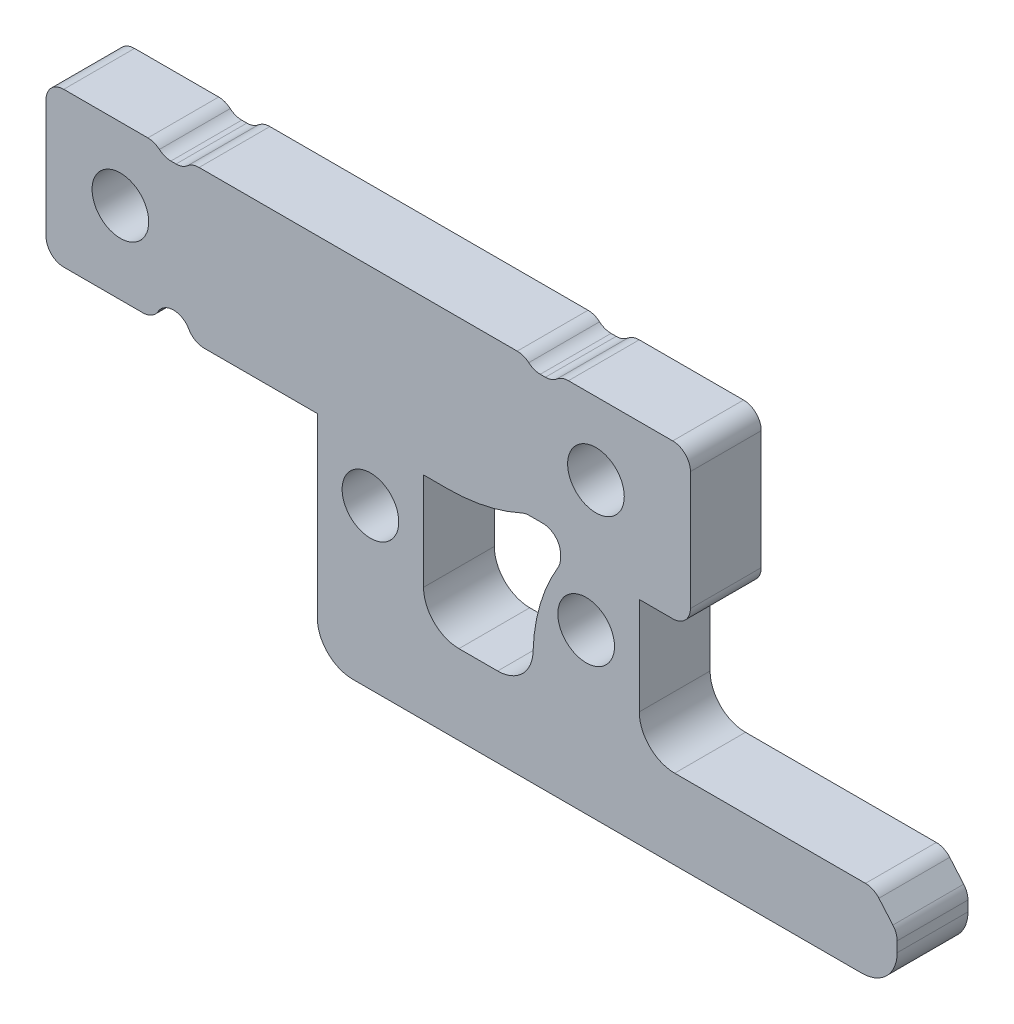
SolidWorks part; units mm, degrees
ref_plane "Plano frontal" through (0, 0, 0) normal (0, 0, 1) x (1, 0, 0)
ref_plane "Plano superior" through (0, 0, 0) normal (0, 1, 0) x (1, 0, 0)
ref_plane "Plano direito" through (0, 0, 0) normal (1, 0, 0) x (0, 0, -1)
sketch "Sketch1" plane through (0, 0, 0) normal (0, 0, 1) x (1, 0, 0)
  line L0 (4.8571, -7) -> (4.8571, 0.8881) construction
  line L2 (-4.2359, -11.5003) -> (-4.2359, 0.5)
  line L3 (1.7641, 0.5) -> (1.7641, -7)
  line L4 (-4.2359, -11.5) -> (-4.2359, -11.5003)
  line L5 (7.95, 0.5) -> (1.7641, 0.5)
  line L6 (16.8395, 9.2) -> (-19.5605, 9.2)
  line L7 (16.8395, 9.2) -> (16.8395, 0.5)
  line L8 (7.95, 0.5) -> (7.95, -7)
  line L9 (16.8395, 0.5) -> (13.95, 0.5)
  line L10 (13.95, -7) -> (13.95, 0.5)
  line L11 (-4.2359, 0.5) -> (-19.5605, 0.5)
  line L12 (-19.5605, 9.2) -> (-19.5605, 0.5)
  line L43 (28.5174, -11.5) -> (28.5174, -8.5479)
  line L44 (28.5174, -8.5479) -> (27.1867, -7)
  line L45 (27.1867, -7) -> (13.95, -7)
  line L49 (28.5174, -11.5) -> (-4.2359, -11.5)
  line L53 (7.95, -7) -> (1.7641, -7)
extrude "Boss-Extrude1" add sketch "Sketch1" along normal blind 4 contours L8 L53 L3 L2 L49 L43 L44 L45 L10 region at (-3.7124, -5.5, 0)
fillet "Fillet1" radius 2 5 edges at (28.5174, -11.5, 2) (13.95, -7, 2) (7.95, -7, 2) (-4.2359, -11.5, 2) (1.7641, -7, 2)
hole_wizard "M3 Clearance Hole1" positions "Sketch3" profile "Sketch2" hole size "M3" standard "ISO" end condition through all
sketch "Sketch3" plane through (0, 0, 4) normal (0, 0, 1) x (1, 0, 0)
  line L0 (4.8571, -7) -> (4.8571, -5.6319) construction
  line L1 (5.95, -7) -> (3.7641, -7) construction
  point P0 (10.95, -2.5)
  point P6 (-1.2359, -2.5)
  point P7 (11.5025, 5.1095)
  point P9 (-15.3605, 5.1095)
sketch "Sketch2" plane through (10.95, -2.5, 4) normal (1, 0, 0) x (0, -1, 0)
  line L0 (0, 0) -> (0, 4)
  line L1 (0, 4) -> (1.6, 4)
  line L2 (1.6, 4) -> (1.6, 0)
  line L5 (1.6, 0) -> (0, 0)
  line L11 (0, -6.35) -> (0, 107.95) construction
  dimension "Thru Hole Dia." = 3.2
  dimension "Thru Hole Depth" = 4
sketch "Sketch4" plane through (0, 0, 4) normal (0, 0, 1) x (1, 0, 0)
  line L0 (16.8395, 9.2) -> (-19.5605, 9.2) construction
  line L1 (9.5025, 8.719) -> (7.5025, 8.719)
  line L2 (9.5025, 8.719) -> (9.5025, 9.2)
  line L3 (9.5025, 9.2) -> (7.5025, 9.2)
  line L4 (7.5025, 8.719) -> (7.5025, 9.2)
  line L5 (-4.2359, 0.5) -> (-19.5605, 0.5) construction
  line L6 (-11.3605, 8.719) -> (-13.3605, 8.719)
  line L7 (-11.3605, 8.719) -> (-11.3605, 9.2)
  line L8 (-11.3605, 9.2) -> (-13.3605, 9.2)
  line L9 (-13.3605, 8.719) -> (-13.3605, 9.2)
  line L10 (-13.3605, 0.5) -> (-11.3605, 0.5)
  line L11 (-13.3605, 0.5) -> (-13.3605, 1.5)
  line L12 (-13.3605, 1.5) -> (-11.3605, 1.5)
  line L13 (-11.3605, 0.5) -> (-11.3605, 1.5)
  line L14 (7.95, 0.5) -> (1.7641, 0.5) construction
  line L16 (7.5025, 0.5) -> (7.5025, 1.5)
  line L17 (7.5025, 1.5) -> (9.5025, 1.5)
  line L18 (9.5025, 0.5) -> (9.5025, 1.5)
  line L21 (9.5025, 0.5) -> (9.5025, 0)
  line L22 (9.5025, 0) -> (7.5025, 0)
  line L23 (7.5025, 0.5) -> (7.5025, 0)
extrude "Cut-Extrude1" cut sketch "Sketch4" against normal blind 10
fillet "Fillet2" radius 10 2 edges at (7.5025, 0.5, 2) (7.95, 0, 2)
fillet "Fillet3" radius 1 15 edges at (28.5174, -8.5479, 2) (27.1867, -7, 2) (-19.5605, 0.5, 2) (-19.5605, 9.2, 2) (16.8395, 9.2, 2) (16.8395, 0.5, 2) (9.5025, 0, 2) (9.5025, 1.5, 2) (7.5025, 1.5, 2) (-13.3605, 8.719, 2) (-11.3605, 8.719, 2) (9.5025, 8.719, 2) (7.5025, 8.719, 2) (-13.3605, 1.5, 2) (-11.3605, 1.5, 2)
fillet "Fillet4" radius 1 6 edges at (-11.3605, 0.5, 2) (-13.3605, 0.5, 2) (-11.3605, 9.2, 2) (-13.3605, 9.2, 2) (9.5025, 9.2, 2) (7.5025, 9.2, 2)
